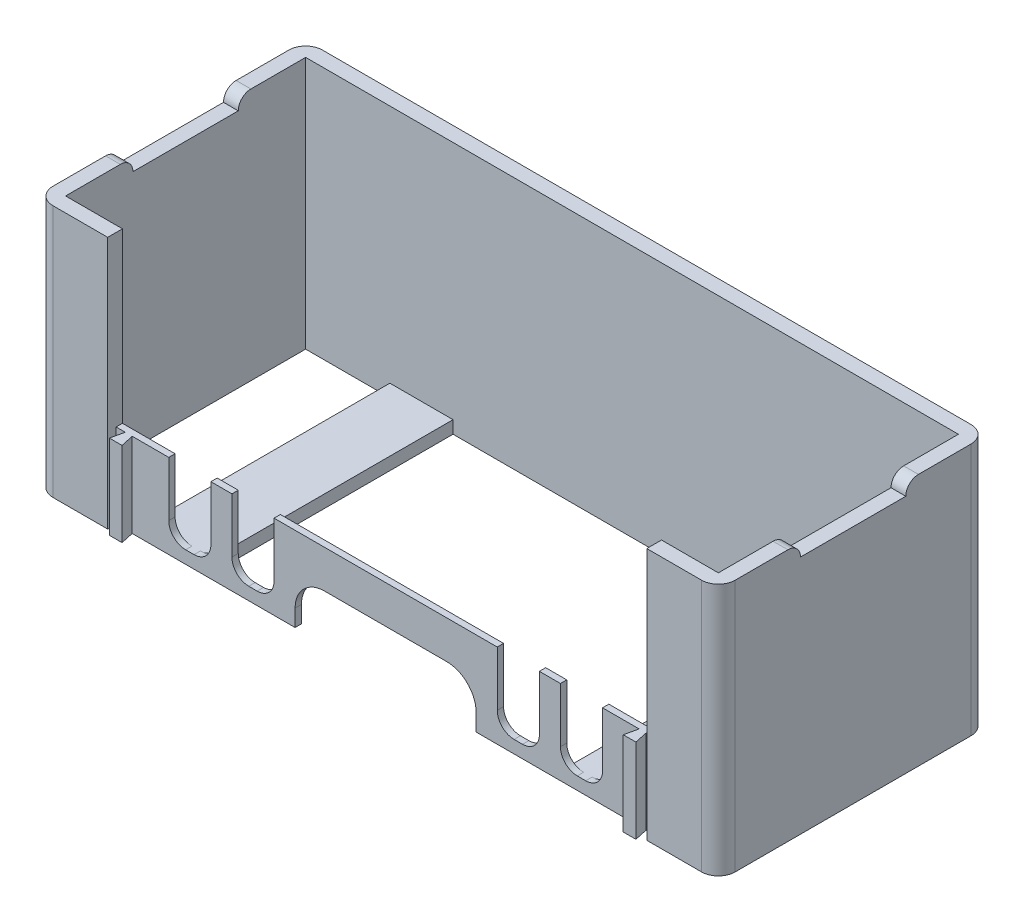
SolidWorks part; units mm, degrees
ref_plane "Front Plane" through (0, 0, 0) normal (0, 0, 1) x (1, 0, 0)
ref_plane "Top Plane" through (0, 0, 0) normal (0, 1, 0) x (1, 0, 0)
ref_plane "Right Plane" through (0, 0, 0) normal (1, 0, 0) x (0, 0, -1)
sketch "Sketch1" plane through (0, 0, 0) normal (0, 1, 0) x (1, 0, 0)
  line L1 (-126.5562, -76.2388) -> (-45.5562, -76.2388)
  line L2 (-126.5562, -76.2388) -> (-126.5562, -44.2388)
  line L3 (-126.5562, -44.2388) -> (-45.5562, -44.2388)
  line L4 (-45.5562, -76.2388) -> (-45.5562, -44.2388)
  dimension "D1" = 81
  dimension "D2" = 32
extrude "Boss-Extrude1" add sketch "Sketch1" along normal blind 10
sketch "Sketch2" plane through (0, 10, 0) normal (0, 1, 0) x (1, 0, 0)
  line L0 (-126.5562, -44.2388) -> (-126.5562, -76.2388) construction
  line L1 (-124.8062, -45.9888) -> (-47.3062, -45.9888)
  line L2 (-124.8062, -45.9888) -> (-124.8062, -74.4888)
  line L3 (-124.8062, -74.4888) -> (-47.3062, -74.4888)
  line L4 (-47.3062, -45.9888) -> (-47.3062, -74.4888)
  line L5 (-45.5562, -44.2388) -> (-126.5562, -44.2388) construction
  line L6 (-45.5562, -76.2388) -> (-45.5562, -44.2388) construction
  line L7 (-126.5562, -76.2388) -> (-45.5562, -76.2388) construction
  dimension "D1" = 1.75
  dimension "D2" = 1.75
  dimension "D3" = 1.75
  dimension "D4" = 1.75
extrude "Cut-Extrude1" cut sketch "Sketch2" against normal blind 10
sketch "Sketch3" plane through (0, 0, 0) normal (0, -1, 0) x (-1, 0, 0)
  line L0 (45.5562, -44.2388) -> (126.5562, -44.2388) construction
  line L1 (57.3062, -44.2388) -> (64.8062, -44.2388)
  line L2 (57.3062, -44.2388) -> (57.3062, -76.2388)
  line L3 (57.3062, -76.2388) -> (64.8062, -76.2388)
  line L4 (64.8062, -44.2388) -> (64.8062, -76.2388)
  line L5 (126.5562, -76.2388) -> (45.5562, -76.2388) construction
  line L6 (124.8062, -45.9888) -> (124.8062, -74.4888) construction
  line L7 (107.3062, -44.2388) -> (114.8062, -44.2388)
  line L8 (107.3062, -44.2388) -> (107.3062, -76.2388)
  line L9 (107.3062, -76.2388) -> (114.8062, -76.2388)
  line L10 (114.8062, -44.2388) -> (114.8062, -76.2388)
  line L11 (47.3062, -74.4888) -> (47.3062, -45.9888) construction
  dimension "D1" = 7.5
  dimension "D2" = 7.5
  dimension "D3" = 10
  dimension "D4" = 10
extrude "Boss-Extrude2" add sketch "Sketch3" against normal blind 1.5
sketch "Sketch4" plane through (0, 10, 0) normal (0, 1, 0) x (1, 0, 0)
  line L0 (-126.5562, -76.2388) -> (-45.5562, -76.2388) construction
  line L1 (-118.0562, -76.2388) -> (-54.0562, -76.2388)
  line L2 (-118.0562, -76.2388) -> (-118.0562, -75.2388)
  line L3 (-118.0562, -75.2388) -> (-54.0562, -75.2388)
  line L4 (-54.0562, -76.2388) -> (-54.0562, -75.2388)
  line L5 (-45.5562, -76.2388) -> (-45.5562, -44.2388) construction
  line L7 (-124.8062, -74.4888) -> (-47.3062, -74.4888) construction
  dimension "D1" = 64
  dimension "D2" = 8.5
  dimension "D3" = 0.75
extrude "Cut-Extrude2" cut sketch "Sketch4" against normal blind 10
sketch "Sketch5" plane through (0, 10, 0) normal (0, 1, 0) x (1, 0, 0)
  line L0 (-116.9762, -75.2388) -> (-117.3062, -76.7818)
  line L1 (-117.3062, -76.7818) -> (-115.8062, -76.7818)
  line L2 (-115.8062, -76.7818) -> (-116.1462, -75.2388)
  line L3 (-116.1462, -75.2388) -> (-116.9762, -75.2388)
  line L4 (-54.0562, -75.2388) -> (-118.0562, -75.2388) construction
  point P2 (-116.5612, -75.2388)
  dimension "D1" = 0.75
  dimension "D2" = 0
  dimension "D3" = 1.08
  dimension "D4" = 1.5
  dimension "D5" = 0.83
  dimension "D6" = 1.58
extrude "Boss-Extrude3" add sketch "Sketch5" against normal blind 10
sketch "Sketch6" plane through (0, 10, 0) normal (0, 1, 0) x (1, 0, 0)
  line L0 (-55.9662, -75.2388) -> (-56.3062, -76.7818)
  line L1 (-54.0562, -75.2388) -> (-116.1462, -75.2388) construction
  line L2 (-56.3062, -76.7818) -> (-54.8062, -76.7818)
  line L3 (-54.8062, -76.7818) -> (-55.1362, -75.2388)
  line L4 (-55.1362, -75.2388) -> (-55.9662, -75.2388)
  dimension "D1" = 1.5
  dimension "D2" = 1.58
  dimension "D3" = 0.83
  dimension "D4" = 0.75
  dimension "D5" = 1.08
extrude "Boss-Extrude4" add sketch "Sketch6" against normal blind 10
fillet "Fillet1" radius 2 1 edges at (-126.5562, 5, 76.2388) type face fillet first side face at (-122.3062, 5, 76.2388) second side face at (-126.5562, 5, 60.2388)
fillet "Fillet2" radius 2 1 edges at (-45.5562, 5, 76.2388) type face fillet first side face at (-49.8062, 5, 76.2388) second side face at (-45.5562, 5, 60.2388)
fillet "Fillet3" radius 2 1 edges at (-45.5562, 5, 44.2388) type face fillet first side face at (-45.5562, 5, 59.2388) second side face at (-86.0562, 5, 44.2388)
fillet "Fillet4" radius 2 1 edges at (-126.5562, 5, 44.2388) type face fillet first side face at (-87.0562, 5, 44.2388) second side face at (-126.5562, 5, 59.2388)
sketch "Sketch7" plane through (0, 0, 75.2388) normal (0, 0, 1) x (1, 0, 0)
  line L0 (-55.9662, 10) -> (-116.1462, 10) construction
  line L1 (-111.8062, 10) -> (-106.8062, 10)
  line L2 (-111.8062, 10) -> (-111.8062, 3.5)
  line L3 (-109.8062, 1.5) -> (-108.8062, 1.5)
  line L4 (-106.8062, 10) -> (-106.8062, 3.5)
  line L5 (-118.0562, 0) -> (-118.0562, 10) construction
  line L6 (-65.3062, 10) -> (-60.3062, 10)
  line L7 (-65.3062, 10) -> (-65.3062, 3.5)
  line L8 (-63.3062, 1.5) -> (-62.3062, 1.5)
  line L9 (-60.3062, 10) -> (-60.3062, 3.5)
  line L10 (-54.0562, 0) -> (-54.0562, 10) construction
  line L11 (-55.9662, 0) -> (-116.1462, 0) construction
  line L13 (-104.3062, 10) -> (-99.3062, 10)
  line L14 (-104.3062, 10) -> (-104.3062, 3.5)
  line L15 (-102.3062, 1.5) -> (-101.3062, 1.5)
  line L16 (-99.3062, 10) -> (-99.3062, 3.5)
  line L17 (-72.8062, 10) -> (-67.8062, 10)
  line L18 (-72.8062, 10) -> (-72.8062, 3.5)
  line L19 (-70.8062, 1.5) -> (-69.8062, 1.5)
  line L20 (-67.8062, 10) -> (-67.8062, 3.5)
  arc A0 (-62.3062, 1.5) -> (-60.3062, 3.5) centre (-62.3062, 3.5) ccw
  arc A1 (-65.3062, 3.5) -> (-63.3062, 1.5) centre (-63.3062, 3.5) ccw
  arc A2 (-69.8062, 1.5) -> (-67.8062, 3.5) centre (-69.8062, 3.5) ccw
  arc A3 (-72.8062, 3.5) -> (-70.8062, 1.5) centre (-70.8062, 3.5) ccw
  arc A4 (-101.3062, 1.5) -> (-99.3062, 3.5) centre (-101.3062, 3.5) ccw
  arc A5 (-104.3062, 3.5) -> (-102.3062, 1.5) centre (-102.3062, 3.5) ccw
  arc A6 (-108.8062, 1.5) -> (-106.8062, 3.5) centre (-108.8062, 3.5) ccw
  arc A7 (-111.8062, 3.5) -> (-109.8062, 1.5) centre (-109.8062, 3.5) ccw
  point P26 (-60.3062, 1.5)
  point P29 (-65.3062, 1.5)
  point P32 (-67.8062, 1.5)
  point P35 (-72.8062, 1.5)
  point P38 (-99.3062, 1.5)
  point P41 (-104.3062, 1.5)
  point P44 (-106.8062, 1.5)
  point P47 (-111.8062, 1.5)
  dimension "D13" = 2
  dimension "D1" = 5
  dimension "D2" = 5
  dimension "D3" = 6.25
  dimension "D4" = 6.25
  dimension "D5" = 1.5
  dimension "D6" = 1.5
  dimension "D7" = 5
  dimension "D8" = 5
  dimension "D9" = 1.5
  dimension "D10" = 1.5
  dimension "D11" = 2.5
  dimension "D12" = 2.5
extrude "Cut-Extrude3" cut sketch "Sketch7" against normal blind 0.75
sketch "Sketch8" plane through (0, 0, 75.2388) normal (0, 0, 1) x (1, 0, 0)
  line L0 (-55.9662, 0) -> (-116.1462, 0) construction
  line L1 (-96.8062, 5.5) -> (-75.3062, 5.5)
  line L2 (-96.8062, 5.5) -> (-96.8062, 0)
  line L3 (-96.8062, 0) -> (-75.3062, 0)
  line L4 (-75.3062, 5.5) -> (-75.3062, 0)
  line L5 (-99.3062, 3.5) -> (-99.3062, 10) construction
  line L6 (-72.8062, 10) -> (-72.8062, 3.5) construction
  dimension "D1" = 5.5
  dimension "D2" = 2.5
  dimension "D3" = 2.5
extrude "Cut-Extrude4" cut sketch "Sketch8" against normal blind 0.75
fillet "Fillet5" radius 3.5 1 edges at (-96.8062, 5.5, 74.8638) type face fillet first side face at (-96.8062, 2.75, 74.8638) second side face at (-86.0562, 5.5, 74.8638)
fillet "Fillet6" radius 3.5 1 edges at (-75.3062, 5.5, 74.8638) type face fillet first side face at (-84.3062, 5.5, 74.8638) second side face at (-75.3062, 2.75, 74.8638)
sketch "Sketch9" plane through (0, 10, 0) normal (0, 1, 0) x (1, 0, 0)
  line L0 (-45.5562, -74.2388) -> (-45.5562, -46.2388) construction
  line L1 (-124.5562, -44.2388) -> (-47.5562, -44.2388)
  line L2 (-126.5562, -46.2388) -> (-126.5562, -74.2388)
  line L3 (-124.5562, -76.2388) -> (-47.5562, -76.2388)
  line L4 (-45.5562, -46.2388) -> (-45.5562, -74.2388)
  line L5 (-126.5562, -46.2388) -> (-126.5562, -74.2388) construction
  line L6 (-47.5562, -44.2388) -> (-124.5562, -44.2388) construction
  line L7 (-124.5562, -76.2388) -> (-118.0562, -76.2388) construction
  line L8 (-118.0562, -75.2388) -> (-118.0562, -76.2388) construction
  line L9 (-124.8062, -45.9888) -> (-47.3062, -45.9888)
  line L10 (-124.8062, -45.9888) -> (-124.8062, -74.4888)
  line L11 (-124.8062, -74.4888) -> (-47.3062, -74.4888)
  line L12 (-47.3062, -45.9888) -> (-47.3062, -74.4888)
  line L13 (-118.0562, -74.4888) -> (-54.0562, -74.4888)
  line L14 (-118.0562, -74.4888) -> (-118.0562, -76.2388)
  line L15 (-118.0562, -76.2388) -> (-54.0562, -76.2388)
  line L16 (-54.0562, -74.4888) -> (-54.0562, -76.2388)
  line L17 (-54.0562, -76.2388) -> (-54.0562, -75.2388) construction
  arc A0 (-47.5562, -44.2388) -> (-45.5562, -46.2388) centre (-47.5562, -46.2388) cw
  arc A1 (-47.5562, -76.2388) -> (-45.5562, -74.2388) centre (-47.5562, -74.2388) ccw
  arc A2 (-126.5562, -74.2388) -> (-124.5562, -76.2388) centre (-124.5562, -74.2388) ccw
  arc A3 (-124.5562, -44.2388) -> (-126.5562, -46.2388) centre (-124.5562, -46.2388) ccw
  line M16 (-124.8062, -74.4888) -> (-124.8062, -45.9888)
  line M17 (-124.8062, -45.9888) -> (-47.3062, -45.9888)
  line M18 (-47.3062, -45.9888) -> (-47.3062, -74.4888)
  line M19 (-47.3062, -74.4888) -> (-60.3062, -74.4888)
  line M26 (-54.0562, -75.2388) -> (-54.0562, -76.2388)
  line M27 (-54.0562, -76.2388) -> (-47.5562, -76.2388)
  arc M28 (-47.5562, -76.2388) -> (-45.5562, -74.2388) centre (-47.5562, -74.2388) ccw
  line M29 (-45.5562, -74.2388) -> (-45.5562, -46.2388)
  arc M30 (-45.5562, -46.2388) -> (-47.5562, -44.2388) centre (-47.5562, -46.2388) ccw
  line M31 (-47.5562, -44.2388) -> (-124.5562, -44.2388)
  arc M32 (-124.5562, -44.2388) -> (-126.5562, -46.2388) centre (-124.5562, -46.2388) ccw
  line M33 (-126.5562, -46.2388) -> (-126.5562, -74.2388)
  arc M34 (-126.5562, -74.2388) -> (-124.5562, -76.2388) centre (-124.5562, -74.2388) ccw
  line M35 (-124.5562, -76.2388) -> (-118.0562, -76.2388)
  line M36 (-118.0562, -76.2388) -> (-118.0562, -75.2388)
  dimension "D5" = 2
  dimension "D1" = 0
  dimension "D2" = 0
  dimension "D3" = 0
  dimension "D4" = 0
  dimension "D6" = 0
  dimension "D7" = 0
extrude "Boss-Extrude5" add sketch "Sketch9" along normal blind 20 contours L16 L14 L11 M19 M26 M27 M28 M29 M30 M31 M32 M33 M34 M35 M36 M16 M17 M18 region at (-86.0562, 10, 45.1097)
sketch "Sketch10" plane through (0, 30, 0) normal (0, 1, 0) x (1, 0, 0)
  line L0 (-47.3062, -45.9888) -> (-47.3062, -74.4888) construction
  line L1 (-47.3062, -66.4888) -> (-45.5562, -66.4888)
  line L2 (-47.3062, -66.4888) -> (-47.3062, -53.9888)
  line L3 (-47.3062, -53.9888) -> (-45.5562, -53.9888)
  line L4 (-45.5562, -66.4888) -> (-45.5562, -53.9888)
  line L5 (-45.5562, -74.2388) -> (-45.5562, -46.2388) construction
  line L6 (-126.5562, -46.2388) -> (-126.5562, -74.2388) construction
  line L7 (-126.5562, -66.4888) -> (-124.8062, -66.4888)
  line L8 (-126.5562, -66.4888) -> (-126.5562, -53.9888)
  line L9 (-126.5562, -53.9888) -> (-124.8062, -53.9888)
  line L10 (-124.8062, -66.4888) -> (-124.8062, -53.9888)
  line L11 (-124.8062, -74.4888) -> (-124.8062, -45.9888) construction
  dimension "D1" = 12.5
  dimension "D2" = 8
  dimension "D3" = 12.5
  dimension "D4" = 8
extrude "Cut-Extrude5" cut sketch "Sketch10" against normal blind 1.5
fillet "Fillet7" radius 1.5 1 edges at (-125.6812, 30, 66.4888) type face fillet first side face at (-125.6812, 29.25, 66.4888) second side face at (-123.4011, 30, 72.7265)
fillet "Fillet8" radius 1.5 1 edges at (-125.6812, 30, 53.9888) type face fillet first side face at (-125.6812, 29.25, 53.9888) second side face at (-86.0562, 30, 48.8059)
fillet "Fillet10" radius 1.5 1 edges at (-46.4312, 30, 53.9888) type face fillet first side face at (-86.0562, 30, 48.5059) second side face at (-46.4312, 29.25, 53.9888)
fillet "Fillet11" radius 1.5 1 edges at (-46.4312, 30, 66.4888) type face fillet first side face at (-48.7113, 30, 72.7265) second side face at (-46.4312, 29.25, 66.4888)
